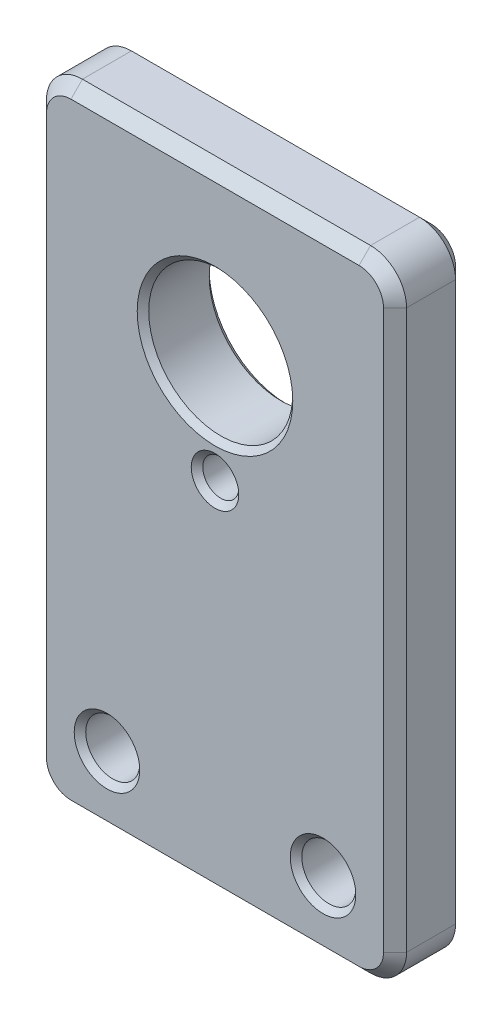
SolidWorks part; units mm, degrees
ref_plane "Front Plane" through (0, 0, 0) normal (0, 0, 1) x (1, 0, 0)
ref_plane "Top Plane" through (0, 0, 0) normal (0, 1, 0) x (1, 0, 0)
ref_plane "Right Plane" through (0, 0, 0) normal (1, 0, 0) x (0, 0, -1)
sketch "Sketch1" plane through (0, 0, 0) normal (0, 0, 1) x (1, 0, 0)
  line L1 (-7.9375, -13.8906) -> (7.9375, -13.8906)
  line L2 (-7.9375, -13.8906) -> (-7.9375, 13.8906)
  line L3 (-7.9375, 13.8906) -> (7.9375, 13.8906)
  line L4 (7.9375, -13.8906) -> (7.9375, 13.8906)
  line L5 (-7.9375, -13.8906) -> (7.9375, 13.8906) construction
  line L6 (-7.9375, 13.8906) -> (7.9375, -13.8906) construction
  point P0 (0, 0)
  dimension "D1" = 27.7812
  dimension "D2" = 15.875
extrude "Boss-Extrude1" add sketch "Sketch1" along normal mid plane 3.175 contours L3 L4 L1 L2
hole_wizard "3/32 (0.09375) Diameter Hole1" positions "Sketch4" profile "Sketch5" hole size "3/32" standard "ANSI Inch" end condition through all
sketch "Sketch4" plane through (0, 0, 1.5875) normal (0, 0, 1) x (1, 0, 0)
  line L0 (-4.7625, -10.7156) -> (4.7625, -10.7156) construction
  line L4 (-7.9375, -13.8906) -> (7.9375, -13.8906) construction
  point P0 (-4.7625, -10.7156)
  point P2 (4.7625, -10.7156)
  point P8 (0, -10.7156)
  dimension "D1" = 9.525
  dimension "D2" = 3.175
sketch "Sketch5" plane through (-4.7625, -10.7156, 1.5875) normal (1, 0, 0) x (0, -1, 0)
  line L0 (0, 0) -> (0, 3.175)
  line L1 (0, 3.175) -> (1.1906, 3.175)
  line L2 (1.1906, 3.175) -> (1.1906, 0)
  line L5 (1.1906, 0) -> (0, 0)
  line L11 (0, -6.35) -> (0, 107.95) construction
  dimension "Thru Hole Dia." = 2.3812
  dimension "Thru Hole Depth" = 3.175
hole_wizard "1/4 (0.25) Diameter Hole1" positions "Sketch2" profile "Sketch3" hole size "1/4" standard "ANSI Inch" end condition through all
sketch "Sketch2" plane through (0, 0, 1.5875) normal (0, 0, 1) x (1, 0, 0)
  circle A0 centre (4.7625, -10.7156) radius 1.1906 construction
  point P0 (0, 6.7469)
  dimension "D1" = 17.4625
sketch "Sketch3" plane through (0, 6.7469, 1.5875) normal (1, 0, 0) x (0, -1, 0)
  line L0 (0, 0) -> (0, 3.175)
  line L1 (0, 3.175) -> (3.175, 3.175)
  line L2 (3.175, 3.175) -> (3.175, 0)
  line L5 (3.175, 0) -> (0, 0)
  line L11 (0, -6.35) -> (0, 107.95) construction
  dimension "Thru Hole Dia." = 6.35
  dimension "Thru Hole Depth" = 3.175
hole_wizard "1/16 (0.0625) Diameter Hole1" positions "Sketch6" profile "Sketch7" hole size "1/16" standard "ANSI Inch" end condition through all
sketch "Sketch6" plane through (0, 0, 1.5875) normal (0, 0, 1) x (1, 0, 0)
  circle A0 centre (0, 6.7469) radius 3.175 construction
  point P0 (0, 1.9844)
  dimension "D1" = 4.7625
sketch "Sketch7" plane through (0, 1.9844, 1.5875) normal (1, 0, 0) x (0, -1, 0)
  line L0 (0, 0) -> (0, 3.175)
  line L1 (0, 3.175) -> (0.7937, 3.175)
  line L2 (0.7937, 3.175) -> (0.7937, 0)
  line L5 (0.7937, 0) -> (0, 0)
  line L11 (0, -6.35) -> (0, 107.95) construction
  dimension "Thru Hole Dia." = 1.5875
  dimension "Thru Hole Depth" = 3.175
fillet "Fillet1" radius 1.5875 4 edges at (7.9375, -13.8906, 0) (-7.9375, -13.8906, 0) (-7.9375, 13.8906, 0) (7.9375, 13.8906, 0)
chamfer "Chamfer1" distance 0.508 angle 45 16 edges at (7.4725, 13.4257, -1.5875) (0, 13.8906, -1.5875) (-7.4725, 13.4257, -1.5875) (-7.9375, 0, -1.5875) (-7.4725, -13.4257, -1.5875) (0, -13.8906, -1.5875) (7.4725, -13.4257, -1.5875) (7.9375, 0, -1.5875) (-7.4725, -13.4257, 1.5875) (-7.9375, 0, 1.5875) (-7.4725, 13.4257, 1.5875) (0, 13.8906, 1.5875) (7.4725, 13.4257, 1.5875) (7.9375, 0, 1.5875) (7.4725, -13.4257, 1.5875) (0, -13.8906, 1.5875)
chamfer "Chamfer2" distance 0.254 angle 45 8 edges at (5.9531, -10.7156, 1.5875) (5.9531, -10.7156, -1.5875) (-3.5719, -10.7156, 1.5875) (-3.5719, -10.7156, -1.5875) (0.7937, 1.9844, 1.5875) (0.7937, 1.9844, -1.5875) (3.175, 6.7469, 1.5875) (3.175, 6.7469, -1.5875)
